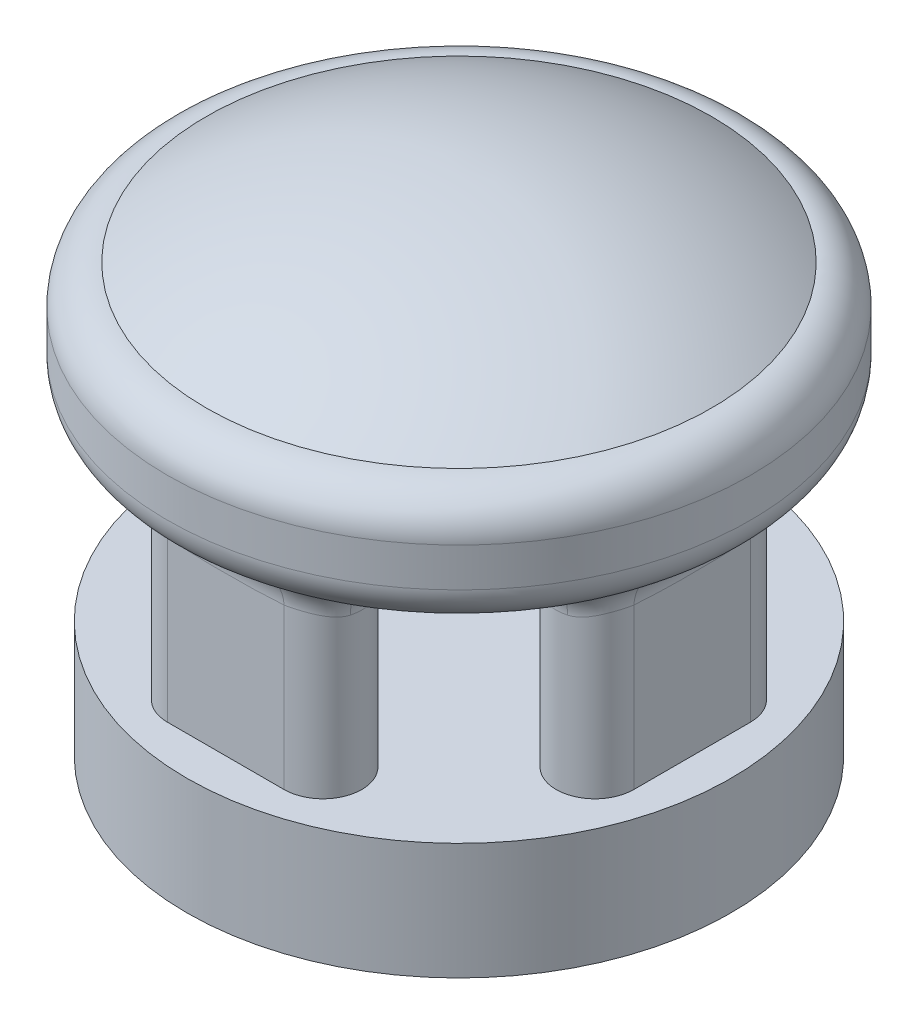
SolidWorks part; units mm, degrees
ref_plane "Front Plane" through (0, 0, 0) normal (0, 0, 1) x (1, 0, 0)
ref_plane "Top Plane" through (0, 0, 0) normal (0, 1, 0) x (1, 0, 0)
ref_plane "Right Plane" through (0, 0, 0) normal (1, 0, 0) x (0, 0, -1)
sketch "Sketch1" plane through (0, 0, 0) normal (0, 1, 0) x (1, 0, 0)
  circle A0 centre (0, 0) radius 9.525
  dimension "D1" = 19.05
extrude "button top" add sketch "Sketch1" along normal blind 3.81
sketch "Sketch2" plane through (0, 0, 0) normal (0, -1, 0) x (1, 0, 0)
  line L9 (-1.905, 6.35) -> (1.905, 6.35) construction
  line L10 (-1.905, 7.62) -> (1.905, 7.62)
  line L11 (-1.905, 5.08) -> (1.905, 5.08)
  arc A6 (-1.905, 7.62) -> (-1.905, 5.08) centre (-1.905, 6.35) ccw
  arc A7 (1.905, 5.08) -> (1.905, 7.62) centre (1.905, 6.35) ccw
  point P22 (0, 6.35)
  dimension "D2" = 1.27
  dimension "D1" = 6.35
  dimension "D8" = 3.81
extrude "connecting leg" add sketch "Sketch2" along normal blind 6.35
ref_axis "central axis" through (0, 3.81, 0) along (0, -1, 0)
pattern_circular "moar legs" count 4 over 360 about axis through (0, 3.81, 0) along (0, -1, 0) of "connecting leg"
ref_plane "base plane" through (0, -6.35, 0) normal (0, -1, 0) x (-1, 0, 0)
sketch "Sketch3" plane through (0, -6.35, 0) normal (0, -1, 0) x (-1, 0, 0)
  circle A0 centre (0, 0) radius 8.89
extrude "base" add sketch "Sketch3" along normal blind 3.81 separate body
fillet "Fillet2" radius 1.27 2 edges at (0, 3.81, 9.525) (0, 0, 9.525)
fillet "Fillet3" radius 1.27 16 edges at (0, 0, 5.08) (-3.175, 0, 6.35) (0, 0, 7.62) (3.175, 0, 6.35) (5.08, 0, 0) (6.35, 0, 3.175) (7.62, 0, 0) (6.35, 0, -3.175) (3.175, 0, -6.35) (0, 0, -7.62) (-3.175, 0, -6.35) (0, 0, -5.08) (-5.08, 0, 0) (-6.35, 0, -3.175) (-7.62, 0, 0) (-6.35, 0, 3.175)
dome "Dome1" faces to dome 1 distance 2.54 reverse direction no elliptical dome no face at (0, 3.81, 8.255) parameters "D1"=2.54
